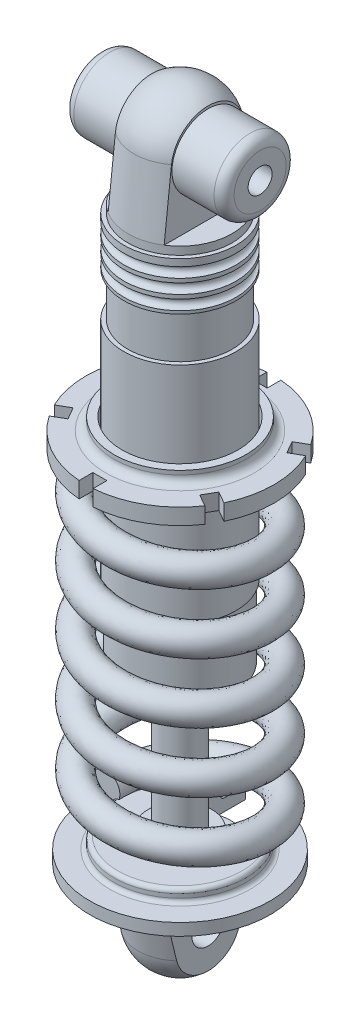
SolidWorks part; units mm, degrees
material "2014 Alloy"
ref_plane "Front Plane" through (0, 0, 0) normal (0, 0, 1) x (1, 0, 0)
ref_plane "Top Plane" through (0, 0, 0) normal (0, 1, 0) x (1, 0, 0)
ref_plane "Right Plane" through (0, 0, 0) normal (1, 0, 0) x (0, 0, -1)
sketch "Sketch1" plane through (0, 0, 0) normal (0, 1, 0) x (1, 0, 0)
  circle A0 centre (0, 0) radius 14
  dimension "D1" = 28
extrude "Extrude1" add sketch "Sketch1" along normal blind 99
sketch "Sketch2" plane through (0, 0, 0) normal (1, 0, 0) x (0, 0, -1)
  line L0 (-14, 0) -> (14, 0) construction
  line L1 (13.5, 0) -> (14, 0)
  line L2 (13.5, 0) -> (13.5, 18)
  line L3 (13.5, 18) -> (14, 18)
  line L4 (14, 0) -> (14, 18)
  line L5 (14, 0) -> (14, 99) construction
  line L6 (0, 0) -> (0, 21.9191) construction
  line L7 (14, 99) -> (-14, 99) construction
  line L8 (14, 85) -> (13, 85)
  line L9 (14, 85) -> (14, 74)
  line L10 (14, 74) -> (13, 74)
  line L11 (13, 85) -> (13, 74)
  line L12 (14, 87) -> (14, 90.5) construction
  line L13 (14, 90.5) -> (14, 94) construction
  line L15 (14, 99) -> (13, 99)
  line L16 (14, 99) -> (14, 97)
  line L17 (14, 97) -> (13, 97)
  line L18 (13, 99) -> (13, 97)
  circle A0 centre (14, 87) radius 1.25
  circle A1 centre (14, 90.5) radius 1.25
  circle A2 centre (14, 94) radius 1.25
  dimension "D6" = 2.5
  dimension "D7" = 2
  dimension "D1" = 18
  dimension "D2" = 27
  dimension "D3" = 26
  dimension "D4" = 11
  dimension "D5" = 14
  dimension "D8" = 3.5
  dimension "D9" = 2
revolve "Cut-Revolve1" cut sketch "Sketch2" angle 360 about L6
sketch "Sketch3" plane through (0, 0, 0) normal (1, 0, 0) x (0, 0, -1)
  line L0 (0, 99) -> (0, 126) construction
  line L1 (13, 99) -> (-13, 99) construction
  line L2 (11.5, 115.4981) -> (13, 99)
  line L3 (13, 99) -> (0, 99)
  line L4 (0, 126) -> (-5.8752, 126) construction
  line L5 (13, 97) -> (13, 99) construction
  line L6 (0, 99) -> (0, 126)
  arc A0 (0, 126) -> (11.5, 115.4981) centre (0, 114.4526) cw
  dimension "D1" = 27
  dimension "D2" = 23
revolve "Revolve1" add sketch "Sketch3" angle 360 about L6
sketch "Sketch4" plane through (0, 0, 0) normal (0, 0, 1) x (1, 0, 0)
  line L0 (0, 97) -> (0, 127) construction
  line L1 (14, 97) -> (-14, 97) construction
  line L2 (-7, 99) -> (-7, 127)
  line L3 (13, 99) -> (7, 99)
  line L4 (13, 99) -> (13, 127)
  line L5 (13, 127) -> (7, 127)
  line L6 (7, 99) -> (7, 127)
  line L7 (-13, 127) -> (-7, 127)
  line L8 (-13, 99) -> (-13, 127)
  line L9 (-13, 99) -> (-7, 99)
  dimension "D1" = 7
  dimension "D2" = 30
extrude "Extrude2" cut sketch "Sketch4" against normal through all and the other way through all
sketch "Sketch6" plane through (0, 0, 0) normal (1, 0, 0) x (0, 0, -1)
  line L0 (0, 114) -> (0, 99) construction
  line L1 (10.9545, 99) -> (-10.9545, 99) construction
  circle A0 centre (0, 114) radius 9
  dimension "D2" = 18
  dimension "D1" = 15
extrude "Extrude3" add sketch "Sketch6" along normal mid plane 40
sketch "Sketch7" plane through (0, 0, 0) normal (1, 0, 0) x (0, 0, -1)
  circle A0 centre (0, 114) radius 3
  dimension "D1" = 6
extrude "Extrude4" cut sketch "Sketch7" against normal through all and the other way through all
sketch "Sketch8" plane through (0, 0, 0) normal (1, 0, 0) x (0, 0, -1)
  line L0 (14.5, 53) -> (14.5, 43)
  line L1 (14.5, 43) -> (15.5, 43)
  line L2 (15.5, 43) -> (15.5, 46)
  line L3 (15.5, 46) -> (23.5, 46)
  line L4 (23.5, 46) -> (23.5, 50)
  line L5 (23.5, 50) -> (16.5, 50)
  line L6 (16.5, 50) -> (16.5, 53)
  line L7 (16.5, 53) -> (14.5, 53)
  line L8 (14, 18) -> (14, 74) construction
  line L9 (0, 74) -> (0, 30.7766) construction
  line L10 (14, 74) -> (-14, 74) construction
  circle A0 centre (0, 114) radius 9 construction
  dimension "D8" = 61
  dimension "D1" = 10
  dimension "D2" = 0.5
  dimension "D3" = 31
  dimension "D4" = 7
  dimension "D5" = 47
  dimension "D6" = 4
  dimension "D7" = 2
revolve "Revolve2" add sketch "Sketch8" angle 360 about L9
fillet "Fillet1" radius 2 1 edges at (0, 50, 16.5)
sketch "Sketch9" plane through (0, 50, 0) normal (0, 1, 0) x (1, 0, 0)
  line L0 (0, 0) -> (0, 20) construction
  line L1 (-1.75, 25) -> (1.75, 25)
  line L2 (-1.75, 25) -> (-1.75, 20)
  line L3 (-1.75, 20) -> (1.75, 20)
  line L4 (1.75, 25) -> (1.75, 20)
  dimension "D1" = 3.5
  dimension "D2" = 20
  dimension "D3" = 5
extrude "Extrude5" cut sketch "Sketch9" against normal blind 10
pattern_circular "CirPattern1" count 6 over 360 about axis through (0, 0, 0) along (0, 1, 0) of "Extrude5"
sketch "Sketch10" plane through (0, 0, 0) normal (0, -1, 0) x (1, 0, 0)
  circle A0 centre (0, 0) radius 5
  dimension "D1" = 10
extrude "Extrude6" add sketch "Sketch10" along normal blind 36
sketch "Sketch11" plane through (0, -36, 0) normal (0, -1, 0) x (1, 0, 0)
  circle A0 centre (0, 0) radius 8
  dimension "D1" = 16
extrude "Extrude7" add sketch "Sketch11" along normal blind 5
sketch "Sketch12" plane through (0, -41, 0) normal (0, -1, 0) x (1, 0, 0)
  circle A0 centre (0, 0) radius 13
  dimension "D1" = 26
extrude "Extrude8" add sketch "Sketch12" along normal blind 3
sketch "Sketch13" plane through (0, 0, 0) normal (1, 0, 0) x (0, 0, -1)
  line L0 (0, -44) -> (-13, -44)
  line L1 (-13, -44) -> (13, -44) construction
  line L2 (-13, -44) -> (-10.5, -57.2909)
  line L3 (0, -66) -> (0, -44)
  line L4 (0, -66) -> (11.6323, -66) construction
  line L5 (0, -44) -> (0, -32.9275) construction
  arc A0 (0, -66) -> (-10.5, -57.2909) centre (0, -55.3159) cw
  dimension "D1" = 22
  dimension "D2" = 10.5
revolve "Revolve3" add sketch "Sketch13" angle 360 about L5
sketch "Sketch14" plane through (0, 0, 0) normal (0, 0, 1) x (1, 0, 0)
  line L0 (0, -66) -> (0, -32.9458) construction
  line L1 (-7, -44) -> (-7, -66)
  line L2 (13, -44) -> (7, -44)
  line L3 (13, -44) -> (13, -66)
  line L4 (13, -66) -> (7, -66)
  line L5 (7, -44) -> (7, -66)
  line L6 (-13, -66) -> (-7, -66)
  line L7 (-13, -44) -> (-13, -66)
  line L8 (-13, -44) -> (-7, -44)
  arc A0 (-10.5, -57.2909) -> (10.5, -57.2909) centre (0, -55.3159) ccw construction
  dimension "D1" = 7
extrude "Extrude9" cut sketch "Sketch14" against normal through all and the other way through all
sketch "Sketch17" plane through (0, 0, 0) normal (1, 0, 0) x (0, 0, -1)
  line L0 (0, -37.5) -> (0, -40.5)
  line L1 (0, -40.5) -> (13.5, -40.5)
  line L2 (13.5, -40.5) -> (13.5, -42.5)
  line L3 (14.5, -43.5) -> (22.5, -43.5)
  line L4 (22.5, -43.5) -> (22.5, -40.5)
  line L5 (22.5, -40.5) -> (17.5, -40.5)
  line L6 (16.5, -39.5) -> (16.5, -38.5)
  line L7 (15.5, -37.5) -> (0, -37.5)
  line L8 (13, -41) -> (-13, -41) construction
  line L9 (13, -44) -> (13, -41) construction
  arc A0 (16.5, -38.5) -> (15.5, -37.5) centre (15.5, -38.5) ccw
  arc A1 (17.5, -40.5) -> (16.5, -39.5) centre (17.5, -39.5) cw
  arc A2 (13.5, -42.5) -> (14.5, -43.5) centre (14.5, -42.5) ccw
  dimension "D6" = 1
  dimension "D8" = 1
  dimension "D1" = 3
  dimension "D2" = 22.5
  dimension "D3" = 0.5
  dimension "D4" = 0.5
  dimension "D5" = 3
  dimension "D7" = 3
revolve "Revolve4" add sketch "Sketch17" angle 360 about L0
sketch "Sketch18" plane through (0, -37.5, 0) normal (0, 1, 0) x (1, 0, 0)
  line L0 (0, 0) -> (0, 4) construction
  line L1 (-5.5, 4) -> (5.5, 4)
  line L2 (-5.5, 4) -> (-5.5, 26)
  line L3 (-5.5, 26) -> (5.5, 26)
  line L4 (5.5, 4) -> (5.5, 26)
  dimension "D1" = 11
  dimension "D2" = 4
  dimension "D3" = 22
extrude "Extrude12" cut sketch "Sketch18" against normal blind 28
sketch "Sketch19" plane through (0, 46, 0) normal (0, -1, 0) x (1, 0, 0)
  circle A0 centre (0, 0) radius 22
  dimension "D1" = 44
curve "Helix/Spiral1" pitch 15 height 78.75 turns 5.25
sketch "Sketch20" plane through (0, 0, 0) normal (1, 0, 0) x (0, 0, -1)
  line L0 (13.2329, 46) -> (23.4347, 46) construction
  line L1 (22, 46) -> (22, 37.6459) construction
  circle A0 centre (18.5, 42.5) radius 3.5
  spline S0 degree 3 poles (22, 46) (22, 45.7601) (21.3232, 45.2771) (18.3701, 44.5552) (13.7472, 43.8325) (7.875, 43.1101) (1.287, 42.3876) (-5.418, 41.6651) (-11.6306, 40.9427) (-16.786, 40.2202) (-20.4158, 39.4977) (-22.1901, 38.7752) (-21.9475, 38.0528) (-19.7102, 37.3303) (-15.6814, 36.6078) (-10.2274, 35.8853) (-3.8438, 35.1628) (2.8891, 34.4404) (9.3595, 33.7179) (14.9792, 32.9954) (19.2374, 32.2729) (21.7472, 31.5505) (22.2804, 30.828) (20.7886, 30.1055) (17.4074, 29.383) (12.444, 28.6606) (6.3496, 27.9381) (-0.3219, 27.2156) (-6.9641, 26.4931) (-12.9734, 25.7706) (-17.8036, 25.0482) (-21.0156, 24.3257) (-22.3175, 23.6032) (-21.591, 22.8807) (-18.9022, 22.1583) (-14.4954, 21.4358) (-8.7711, 20.7133) (-2.2496, 19.9908) (4.4763, 19.2683) (10.7954, 18.5459) (16.1334, 17.8234) (20.0049, 17.1009) (22.0583, 16.3784) (22.1068, 15.656) (20.1461, 14.9335) (16.3543, 14.211) (11.0761, 13.4885) (4.7913, 12.7661) (-1.9291, 12.0436) (-8.4741, 11.3211) (-14.2489, 10.5986) (-18.7287, 9.8761) (-21.5062, 9.1537) (-22.3291, 8.4312) (-21.1225, 7.7087) (-17.9961, 6.9862) (-13.2341, 6.2638) (-7.2693, 5.5413) (-0.6437, 4.8188) (6.0403, 4.0963) (12.1754, 3.3739) (17.2038, 2.6514) (20.6686, 1.9289) (22.2549, 1.2064) (21.8185, 0.4839) (19.399, -0.2385) (15.2164, -0.961) (9.6508, -1.6835) (3.208, -2.406) (-3.5263, -3.1284) (-9.9401, -3.8509) (-15.4505, -4.5734) (-19.5566, -5.2959) (-21.8853, -6.0183) (-22.2248, -6.7408) (-20.5444, -7.4633) (-16.9967, -8.1858) (-11.9042, -8.9083) (-5.7298, -9.6307) (0.9655, -10.3532) (7.5729, -11.0757) (13.4921, -11.7982) (18.185, -12.5206) (21.2251, -13.2431) (22.3361, -13.9656) (21.417, -14.6881) (18.5513, -15.4106) (13.9995, -16.133) (8.1754, -16.8555) (1.6082, -17.578) (-5.1052, -18.3005) (-11.3545, -19.0229) (-16.5719, -19.7454) (-20.2831, -20.4679) (-22.1508, -21.1904) (-22.0052, -21.9128) (-19.8596, -22.6353) (-15.909, -23.3578) (-10.5125, -24.0803) (-4.1605, -24.8028) (2.5696, -25.5252) (9.0662, -26.2477) (14.7388, -26.9702) (19.0718, -27.6927) (21.6714, -28.4151) (22.3013, -29.1376) (20.9042, -29.8601) (17.6076, -30.5825) (12.709, -31.3052) (6.6614, -32.0271) (2.2109, -32.5101) (0, -32.75) knots 0 0 0 0 0.009174 0.018349 0.027523 0.036697 0.045872 0.055046 0.06422 0.073394 0.082569 0.091743 0.100917 0.110092 0.119266 0.12844 0.137615 0.146789 0.155963 0.165138 0.174312 0.183486 0.192661 0.201835 0.211009 0.220183 0.229358 0.238532 0.247706 0.256881 0.266055 0.275229 0.284404 0.293578 0.302752 0.311927 0.321101 0.330275 0.33945 0.348624 0.357798 0.366972 0.376147 0.385321 0.394495 0.40367 0.412844 0.422018 0.431193 0.440367 0.449541 0.458716 0.46789 0.477064 0.486239 0.495413 0.504587 0.513761 0.522936 0.53211 0.541284 0.550459 0.559633 0.568807 0.577982 0.587156 0.59633 0.605505 0.614679 0.623853 0.633028 0.642202 0.651376 0.66055 0.669725 0.678899 0.688073 0.697248 0.706422 0.715596 0.724771 0.733945 0.743119 0.752294 0.761468 0.770642 0.779817 0.788991 0.798165 0.807339 0.816514 0.825688 0.834862 0.844037 0.853211 0.862385 0.87156 0.880734 0.889908 0.899083 0.908257 0.917431 0.926606 0.93578 0.944954 0.954128 0.963303 0.972477 0.981651 0.990826 1 1 1 1 construction
  dimension "D1" = 7
sweep "Sweep2" add profiles "Sketch20" path "Helix/Spiral1"
sketch "Sketch21" plane through (0, 0, 0) normal (0, 0, 1) x (1, 0, 0)
  line L0 (-29.0751, 18) -> (31.4708, 18)
  line L1 (-13.5, 18) -> (13.5, 18) construction
extrude "Extrude13" [suppressed] cut sketch "Sketch21" against normal through all and the other way through all
fillet "Fillet2" radius 2.5 2 edges at (20, 114, -9) (-20, 114, -9)
sketch "Sketch22" plane through (7, 0, 0) normal (1, 0, 0) x (0, 0, -1)
  line L0 (-10.9545, -44) -> (10.9545, -44) construction
  circle A0 centre (0, -54) radius 4
  arc A1 (-7.8262, -57.2909) -> (7.8262, -57.2909) centre (0, -55.3159) ccw construction
  dimension "D1" = 10
extrude "Cut-Extrude3" cut sketch "Sketch22" against normal through all contours A0
equation "\"Lenght\"=0"
